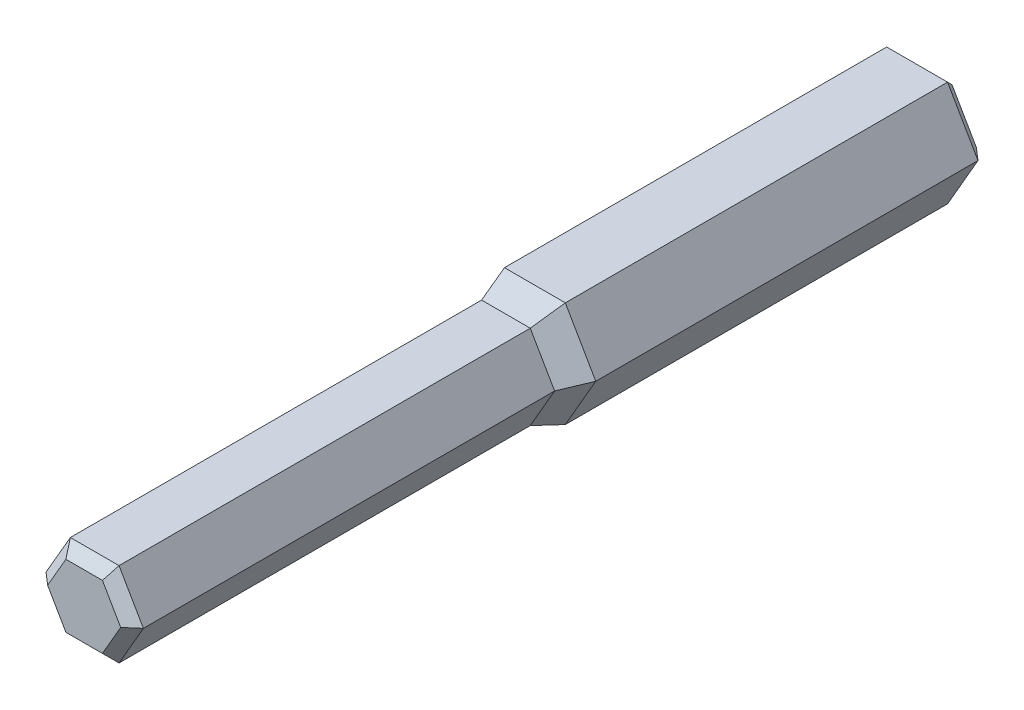
SolidWorks part; units mm, degrees
ref_plane "前视基准面" through (0, 0, 0) normal (0, 0, 1) x (1, 0, 0)
ref_plane "上视基准面" through (0, 0, 0) normal (0, 1, 0) x (1, 0, 0)
ref_plane "右视基准面" through (0, 0, 0) normal (1, 0, 0) x (0, 0, -1)
sketch "草图1" plane through (0, 0, 0) normal (0, 0, 1) x (1, 0, 0)
  line L1 (2.3094, 0) -> (1.1547, 2)
  line L2 (1.1547, 2) -> (-1.1547, 2)
  line L3 (-1.1547, 2) -> (-2.3094, 0)
  line L4 (-2.3094, 0) -> (-1.1547, -2)
  line L5 (-1.1547, -2) -> (1.1547, -2)
  line L6 (1.1547, -2) -> (2.3094, 0)
  circle A0 centre (0, 0) radius 2 construction
  dimension "D1" = 4
extrude "凸台-拉伸1" add sketch "草图1" along normal blind 20
chamfer "倒角1" distance 0.5 angle 45 6 edges at (0, -2, 20) (-1.7321, -1, 20) (-1.7321, 1, 20) (0, 2, 20) (1.7321, 1, 20) (1.7321, -1, 20)
sketch "草图2" plane through (0, 0, 0) normal (0, 0, -1) x (-1, 0, 0)
  line L1 (2.8868, 0) -> (1.4434, 2.5)
  line L2 (1.4434, 2.5) -> (-1.4434, 2.5)
  line L3 (-1.4434, 2.5) -> (-2.8868, 0)
  line L4 (-2.8868, 0) -> (-1.4434, -2.5)
  line L5 (-1.4434, -2.5) -> (1.4434, -2.5)
  line L6 (1.4434, -2.5) -> (2.8868, 0)
  circle A0 centre (0, 0) radius 2.5 construction
  dimension "D1" = 5
extrude "凸台-拉伸2" add sketch "草图2" along normal blind 20
chamfer "倒角3" distance 0.5 angle 70 6 edges at (-2.1651, 1.25, 0) (-2.1651, -1.25, 0) (0, -2.5, 0) (2.1651, -1.25, 0) (2.1651, 1.25, 0) (0, 2.5, 0) first distance on face at (0, 0, 0)
chamfer "倒角4" distance 0.5 angle 45 6 edges at (0, -2.5, -20) (2.1651, -1.25, -20) (2.1651, 1.25, -20) (0, 2.5, -20) (-2.1651, 1.25, -20) (-2.1651, -1.25, -20)
